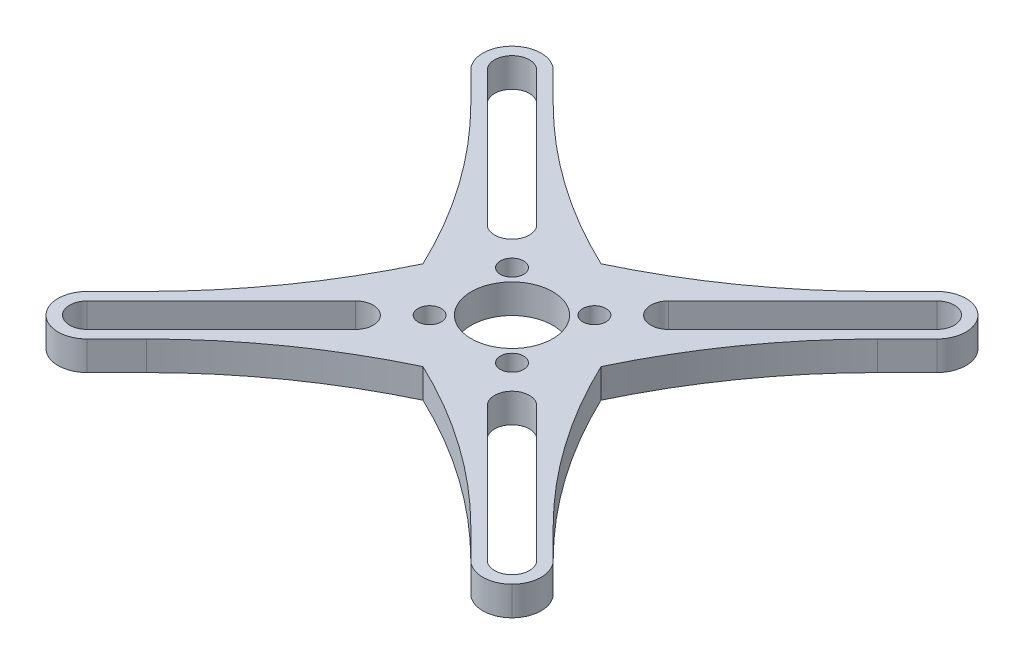
SolidWorks part; units mm, degrees
ref_plane "Front Plane" through (0, 0, 0) normal (0, 0, 1) x (1, 0, 0)
ref_plane "Top Plane" through (0, 0, 0) normal (0, 1, 0) x (1, 0, 0)
ref_plane "Right Plane" through (0, 0, 0) normal (1, 0, 0) x (0, 0, -1)
sketch "Sketch1" plane through (0, 0, 0) normal (0, 1, 0) x (1, 0, 0)
  line L0 (0, 0) -> (11.2462, 11.2462)
  circle A0 centre (0, 0) radius 14
  circle A1 centre (0, 0) radius 10
  circle A2 centre (7.0711, 7.0711) radius 2
  circle A3 centre (7.0711, -7.0711) radius 2
  circle A4 centre (-7.0711, -7.0711) radius 2
  circle A5 centre (-7.0711, 7.0711) radius 2
  circle A6 centre (0, 0) radius 7
  dimension "D1" = 28
  dimension "D2" = 20
  dimension "D3" = 4
  dimension "D5" = 14
  dimension "D4" = 4
extrude "Boss-Extrude1" add sketch "Sketch1" along normal blind 5 contours A5 A1 A2 A0 A3 A4 | A6 A2 A1 A5 A4 A3 region at (6.9568, 0, -4.7911) region at (12.5685, 0, -5.206)
sketch "Sketch4" plane through (0, 5, 0) normal (0, 1, 0) x (1, 0, 0)
  line L0 (0, 0) -> (-40, 40)
  line L1 (0, 0) -> (9.8995, 9.8995)
  line L2 (0, 0) -> (9.8995, -9.8995)
  line L3 (0, 0) -> (-9.8995, -9.8995)
  line L4 (-3.5355, -3.5355) -> (3.5355, 3.5355)
  line L5 (-3.5355, -3.5355) -> (-43.5355, 36.4645)
  line L6 (3.5355, 3.5355) -> (-36.4645, 43.5355)
  line L7 (-43.5355, 36.4645) -> (-36.4645, 43.5355)
  line L8 (-13.4205, 13.4205) -> (-36.4645, 36.4645) construction
  line L9 (-15.5418, 11.2992) -> (-38.5858, 34.3431)
  line L10 (-11.2992, 15.5418) -> (-34.3431, 38.5858)
  line L11 (-6.3495, 13.4205) -> (-13.4205, 6.3495)
  line L12 (-3.5355, 3.5355) -> (36.4645, 43.5355)
  line L13 (3.5355, -3.5355) -> (43.5355, 36.4645)
  line L14 (36.4645, 43.5355) -> (43.5355, 36.4645)
  line L15 (13.4205, 13.4205) -> (36.4645, 36.4645) construction
  line L16 (11.2992, 15.5418) -> (34.3431, 38.5858)
  line L17 (15.5418, 11.2992) -> (38.5858, 34.3431)
  line L18 (3.5355, 3.5355) -> (43.5355, -36.4645)
  line L19 (-3.5355, -3.5355) -> (36.4645, -43.5355)
  line L20 (43.5355, -36.4645) -> (36.4645, -43.5355)
  line L21 (13.4205, -13.4205) -> (36.4645, -36.4645) construction
  line L22 (15.5418, -11.2992) -> (38.5858, -34.3431)
  line L23 (11.2992, -15.5418) -> (34.3431, -38.5858)
  line L24 (3.5355, -3.5355) -> (-36.4645, -43.5355)
  line L25 (-3.5355, 3.5355) -> (-43.5355, -36.4645)
  line L26 (-36.4645, -43.5355) -> (-43.5355, -36.4645)
  line L27 (-13.4205, -13.4205) -> (-36.4645, -36.4645) construction
  line L28 (-11.2992, -15.5418) -> (-34.3431, -38.5858)
  line L29 (-15.5418, -11.2992) -> (-38.5858, -34.3431)
  circle A0 centre (0, 0) radius 14
  arc A1 (-15.5418, 11.2992) -> (-11.2992, 15.5418) centre (-13.4205, 13.4205) ccw
  arc A2 (-34.3431, 38.5858) -> (-38.5858, 34.3431) centre (-36.4645, 36.4645) ccw
  arc A3 (11.2992, 15.5418) -> (15.5418, 11.2992) centre (13.4205, 13.4205) ccw
  arc A4 (38.5858, 34.3431) -> (34.3431, 38.5858) centre (36.4645, 36.4645) ccw
  arc A5 (15.5418, -11.2992) -> (11.2992, -15.5418) centre (13.4205, -13.4205) ccw
  arc A6 (34.3431, -38.5858) -> (38.5858, -34.3431) centre (36.4645, -36.4645) ccw
  arc A7 (-11.2992, -15.5418) -> (-15.5418, -11.2992) centre (-13.4205, -13.4205) ccw
  arc A8 (-38.5858, -34.3431) -> (-34.3431, -38.5858) centre (-36.4645, -36.4645) ccw
  point P4 (-24.9425, 24.9425)
  point P20 (-9.885, 9.885)
  point P26 (24.9425, 24.9425)
  point P37 (24.9425, -24.9425)
  point P48 (-24.9425, -24.9425)
  circle M9 centre (0, 0) radius 14
  dimension "D2" = 40
  dimension "D3" = 10
  dimension "D4" = 6
  dimension "D5" = 5
  dimension "D6" = 5
  dimension "D7" = 5
  dimension "D1" = 4
  dimension "D8" = 4
extrude "Boss-Extrude3" add sketch "Sketch4" against normal blind 5 contours L26 L24 L25 A8 L29 A7 L28 M9 | A2 L0 L7 L5 L11 A1 L9 M9 | L11 L5 M9 | A2 L10 A1 L0 L11 L6 L7 M9 | L6 L11 M9 | L14 L12 L13 A4 L17 A3 L16 M9 | L20 L18 L19 A6 L23 A5 L22 M9 region at (8.2405, 5, -11.9732) region at (11.9732, 5, 8.2405) region at (-8.2405, 5, 11.9732) region at (-27.5176, 5, -22.3705) region at (-22.3705, 5, -27.5176) region at (-6.9889, 5, -12.3964) region at (-12.3964, 5, -6.9889)
fillet "Fillet1" radius 5 8 edges at (-36.4645, 2.5, 43.5355) (-43.5355, 2.5, 36.4645) (-43.5355, 2.5, -36.4645) (-36.4645, 2.5, -43.5355) (36.4645, 2.5, -43.5355) (43.5355, 2.5, -36.4645) (36.4645, 2.5, 43.5355) (43.5355, 2.5, 36.4645)
fillet "Fillet2" radius 100 8 edges at (-5.7111, 2.5, 12.7822) (5.7111, 2.5, 12.7822) (12.7822, 2.5, 5.7111) (12.7822, 2.5, -5.7111) (-5.7111, 2.5, -12.7822) (5.7111, 2.5, -12.7822) (-12.7822, 2.5, -5.7111) (-12.7822, 2.5, 5.7111)
